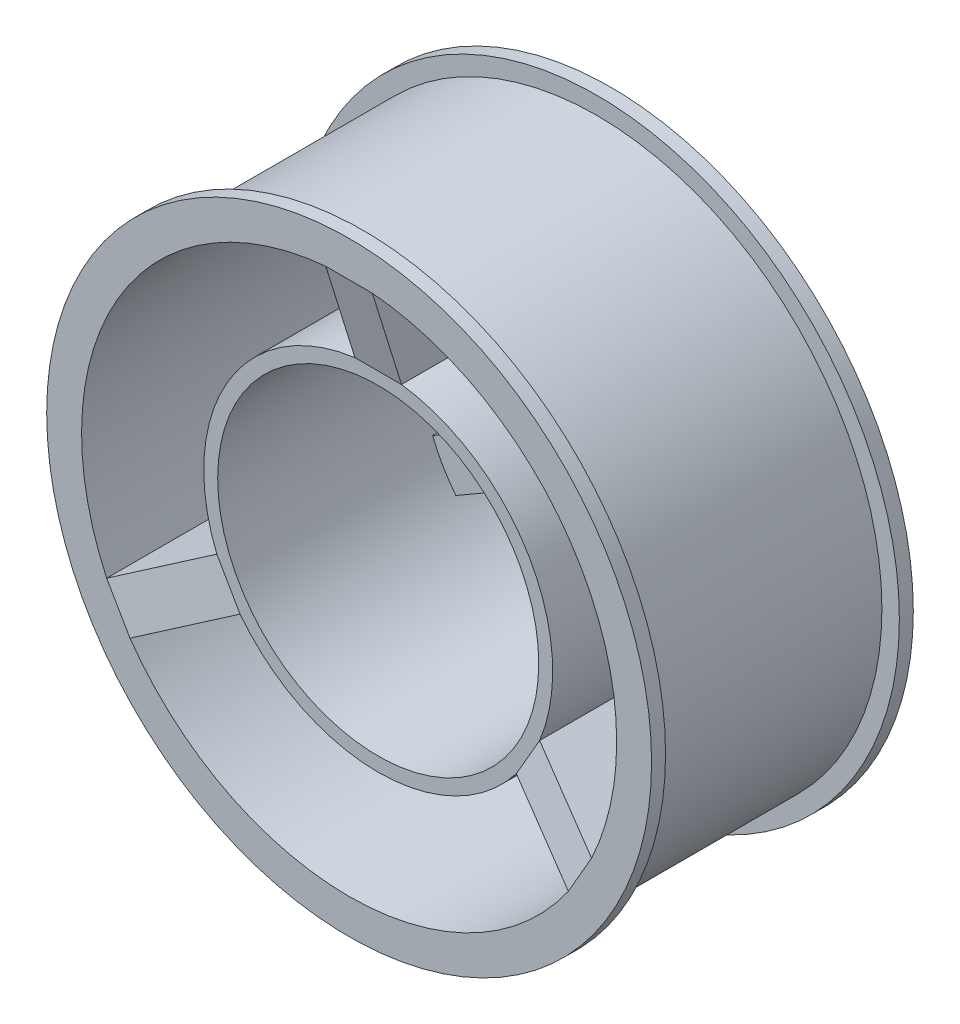
SolidWorks part; units mm, degrees
ref_plane "前视基准面" through (0, 0, 0) normal (0, 0, 1) x (1, 0, 0)
ref_plane "上视基准面" through (0, 0, 0) normal (0, 1, 0) x (1, 0, 0)
ref_plane "右视基准面" through (0, 0, 0) normal (1, 0, 0) x (0, 0, -1)
other "Configuration Table"
sketch "Sketch1" plane through (0, 0, 0) normal (0, 0, 1) x (1, 0, 0)
  circle A0 centre (0, 0) radius 24.5
  circle A2 centre (0, 0) radius 23
extrude "Boss-Extrude1" add sketch "Sketch1" along normal blind 22.5 and the other way blind 0.0001
sketch "Sketch4" plane through (0, 0, 0) normal (0, 0, 1) x (1, 0, 0)
  circle A0 centre (0, 0) radius 26
  circle A1 centre (0, 0) radius 23
extrude "Boss-Extrude2" add sketch "Sketch4" along normal blind 1.2
sketch "Sketch7" plane through (0, 0, 22.5) normal (0, 0, 1) x (1, 0, 0)
  circle A0 centre (0, 0) radius 26
  circle A1 centre (-0.2461, 0) radius 24.2539
extrude "Boss-Extrude4" add sketch "Sketch7" against normal blind 1.2
sketch "Sketch8" plane through (0, 0, 0) normal (0, 0, 1) x (1, 0, 0)
  circle A0 centre (0, 0) radius 13.8
  circle A1 centre (0, 0) radius 15
extrude "Boss-Extrude5" add sketch "Sketch8" along normal blind 20 separate body
sketch "Sketch9" plane through (0, 0, 0) normal (0, 0, 1) x (1, 0, 0)
  circle A0 centre (0, 0) radius 10
extrude "Boss-Extrude6" add sketch "Sketch9" along normal blind 1 separate body
sketch "Sketch11" plane through (0, 0, 0) normal (0, 1, 0) x (1, 0, 0)
  line L1 (-2, 0) -> (2, 0)
  line L2 (-2, 0) -> (-2, -2.5)
  line L3 (-2, -2.5) -> (2, -2.5)
  line L4 (2, 0) -> (2, -2.5)
  dimension "D1" = 4
  dimension "D2" = 2
  dimension "D3" = 0
  dimension "D4" = 2.5
extrude "Boss-Extrude8" add sketch "Sketch11" along normal blind 24
sketch "Sketch13" plane through (0, 0, 2.5) normal (0, 0, 1) x (1, 0, 0)
  circle A0 centre (0, 0) radius 4.65
sketch "Sketch19" plane through (0, 0, 2.5) normal (0, 0, 1) x (1, 0, 0)
  line L0 (-2, 22.9129) -> (-2, 14.8661) construction
  line L1 (-2, 23.9255) -> (2, 23.9255)
  line L2 (-2, 23.9255) -> (-2, 14.5751)
  line L3 (-2, 14.5751) -> (2, 14.5751)
  line L4 (2, 23.9255) -> (2, 14.5751)
  dimension "D1" = 4
  dimension "D2" = 0
extrude "Boss-Extrude9" add sketch "Sketch19" along normal through all
sketch "Sketch20" plane through (-2, 0, 0) normal (-1, 0, 0) x (0, 0, 1)
  line L0 (20, 14.8661) -> (22.5, 22.9129)
  line L1 (22.5, 22.9129) -> (22.5, 14.5751)
  line L2 (22.5, 14.5751) -> (20, 14.5751) construction
  line L3 (22.5, 22.9129) -> (22.5, 14.5751) construction
  line L4 (22.5, 14.5751) -> (20, 14.5751)
  line L5 (20, 14.5751) -> (20, 14.8661)
extrude "Cut-Extrude7" cut sketch "Sketch13" against normal blind 1.5 contours A0
pattern_circular "CirPattern2" count 3 over 360 about axis through (0, 0, 1) along (0, 0, -1) of "Boss-Extrude8" reverse direction yes
sketch "Sketch21" plane through (0, 0, 2.5) normal (0, 0, 1) x (1, 0, 0)
  circle A0 centre (0, 0) radius 4.65
extrude "Cut-Extrude8" cut sketch "Sketch21" against normal blind 1.5 contours A0
pattern_circular "CirPattern6" count 3 over 360 about axis through (0, 0, 20) along (0, 0, -1) of "Boss-Extrude9"
sketch "Sketch23" plane through (0, 0, 0) normal (0, 0, -1) x (-1, 0, 0)
  circle A0 centre (0, 0) radius 6
  circle A1 centre (0, 6) radius 1.1
extrude "Cut-Extrude9" cut sketch "Sketch23" against normal blind 3.5 contours A1
pattern_circular "CirPattern8" count 3 over 360 about axis through (0, 0, 1) along (0, 0, -1) of "Cut-Extrude9"
sketch "Sketch24" plane through (2, 0, 0) normal (1, 0, 0) x (0, 0, -1)
extrude "Cut-Extrude11" cut sketch "Sketch20" against normal blind 4 contours L0 L1 L4 L5
pattern_circular "CirPattern9" count 3 every 120 about axis through (0, 0, 20) along (0, 0, -1) of "Cut-Extrude11"
sketch "Sketch27" plane through (0, 0, 0) normal (0, 0, -1) x (-1, 0, 0)
  circle A0 centre (0, 0) radius 10
sketch "Sketch28" plane through (0, 0, 0) normal (0, 0, -1) x (-1, 0, 0)
  circle A0 centre (0, 0) radius 10
extrude "Boss-Extrude10" add sketch "Sketch27" along normal blind 4
sketch "Sketch29" plane through (0, 0, -4) normal (0, 0, -1) x (-1, 0, 0)
  circle A0 centre (0, 0) radius 6
extrude "Boss-Extrude11" add sketch "Sketch29" along normal blind 4
sketch "Sketch30" plane through (0, 0, 1) normal (0, 0, 1) x (1, 0, 0)
  circle A0 centre (0, 6) radius 1.1
extrude "Cut-Extrude12" cut sketch "Sketch30" against normal blind 13 contours A0
sketch "Sketch31" plane through (0, 0, 1) normal (0, 0, 1) x (1, 0, 0)
  circle A0 centre (5.1962, -3) radius 1.1
  circle A1 centre (-5.1962, -3) radius 1.1
extrude "Cut-Extrude13" cut sketch "Sketch31" against normal blind 13 contours A1 | A0
sketch "Sketch32" plane through (0, 0, -8) normal (0, 0, -1) x (-1, 0, 0)
  circle A0 centre (0, 6) radius 1.9
extrude "Cut-Extrude14" cut sketch "Sketch32" against normal blind 7.5 contours A0
sketch "Sketch35" plane through (0, 0, 1) normal (0, 0, 1) x (1, 0, 0)
  line L1 (1.5877, -2.75) -> (3.1754, 0)
  line L2 (3.1754, 0) -> (1.5877, 2.75)
  line L3 (1.5877, 2.75) -> (-1.5877, 2.75)
  line L4 (-1.5877, 2.75) -> (-3.1754, 0)
  line L5 (-3.1754, 0) -> (-1.5877, -2.75)
  line L6 (-1.5877, -2.75) -> (1.5877, -2.75)
  circle A0 centre (0, 0) radius 2.75 construction
extrude "Cut-Extrude15" cut sketch "Sketch35" against normal blind 2.5 contours L3 L4 L5 L6 L1 L2
sketch "Sketch36" plane through (0, 0, -8) normal (0, 0, -1) x (-1, 0, 0)
  circle A0 centre (0, 0) radius 1.6
extrude "Cut-Extrude16" cut sketch "Sketch36" against normal blind 18.5 contours A0
sketch "Sketch40" plane through (0, 0, -4) normal (0, 0, -1) x (-1, 0, 0)
  circle A0 centre (0, 0) radius 7.25
extrude "Boss-Extrude13" add sketch "Sketch40" along normal blind 0.5 contours A0
extrude "Cut-Extrude17" cut sketch "Sketch36<4>" against normal blind 8.5
sketch "Sketch36<4>" plane through (0, 0, -8) normal (0, 0, -1) x (-1, 0, 0) same geometry as "Sketch36"
extrude "Cut-Extrude18" cut sketch "Sketch32<3>" against normal blind 4.5
sketch "Sketch32<3>" plane through (0, 0, -8) normal (0, 0, -1) x (-1, 0, 0) same geometry as "Sketch32"
pattern_circular "CirPattern10" count 3 every 120 about axis through (0, 0, -8) along (0, 0, 1) of "Cut-Extrude14"
